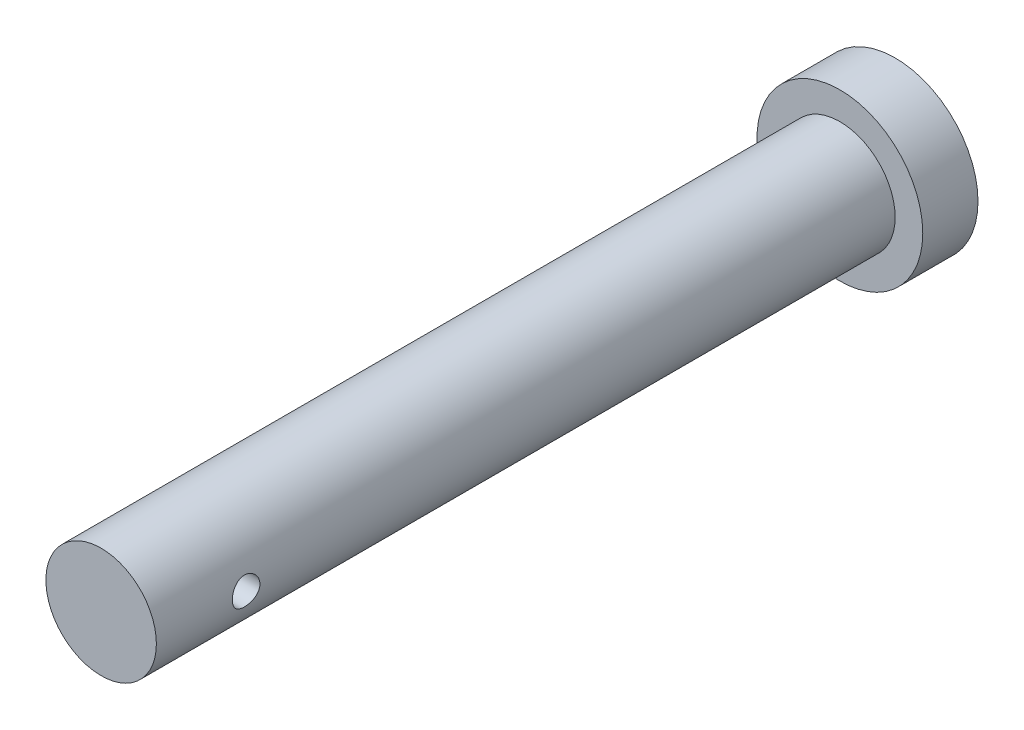
SolidWorks part; units mm, degrees
ref_plane "Front Plane" through (0, 0, 0) normal (0, 0, 1) x (1, 0, 0)
ref_plane "Top Plane" through (0, 0, 0) normal (0, 1, 0) x (1, 0, 0)
ref_plane "Right Plane" through (0, 0, 0) normal (1, 0, 0) x (0, 0, -1)
sketch "Sketch1" plane through (0, 0, 0) normal (0, 0, 1) x (1, 0, 0)
  circle A0 centre (0, 0) radius 12
  circle A1 centre (0, 0) radius 8
  dimension "D1" = 24
  dimension "D2" = 16
extrude "Boss-Extrude1" add sketch "Sketch1" along normal blind 8 contours A1 | A0 A1 region at (-11.6606, 0, 0) region at (0, 0, 0)
extrude "Boss-Extrude2" add sketch "Sketch1<3>" along normal blind 115 contours A1 region at (0, 0, 0)
sketch "Sketch1<3>" plane through (0, 0, 0) normal (0, 0, 1) x (1, 0, 0) same geometry as "Sketch1"
sketch "Sketch3" plane through (0, 0, 0) normal (1, 0, 0) x (0, 0, -1)
  line L0 (-8, 8) -> (-8, -8) construction
  circle A0 centre (-102, 0) radius 2
  point P4 (-102, 0)
  point P5 (0, 0)
  dimension "D1" = 4
  dimension "D2" = 94
extrude "Cut-Extrude1" cut sketch "Sketch3" against normal blind 100 and the other way blind 100
